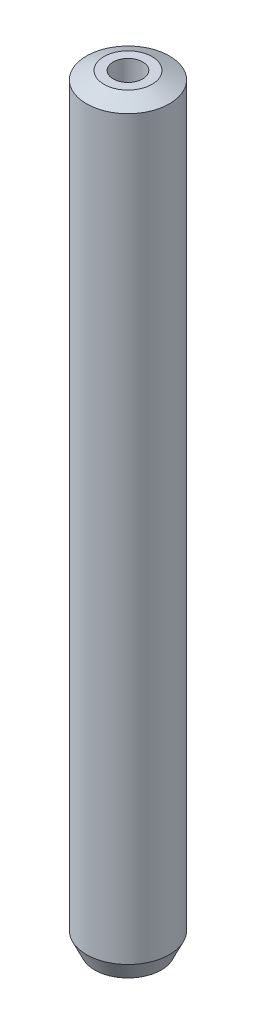
SolidWorks part; units mm, degrees
ref_plane "Front Plane" through (0, 0, 0) normal (0, 0, 1) x (1, 0, 0)
ref_plane "Top Plane" through (0, 0, 0) normal (0, 1, 0) x (1, 0, 0)
ref_plane "Right Plane" through (0, 0, 0) normal (1, 0, 0) x (0, 0, -1)
sketch "Sketch1" plane through (0, 0, 0) normal (0, 1, 0) x (1, 0, 0)
  circle A0 centre (0, 0) radius 7.5
  dimension "SHAFT_OD" = 15
extrude "Boss-Extrude1" add sketch "Sketch1" along normal blind 137.8778
sketch "Sketch2" plane through (0, 0, 0) normal (0, 1, 0) x (1, 0, 0)
  circle A0 centre (0, 0) radius 2.6673
  dimension "BORE_D" = 5.3345
extrude "Cut-Extrude1" cut sketch "Sketch2" along normal through all
chamfer "Chamfer1" distance 1.4738 angle 64.946 2 edges at (0, 137.8778, 7.5) (0, 0, 7.5) first distance on face at (0, 137.8778, 7.5) first distance on face at (0, 0, 2.6673)
